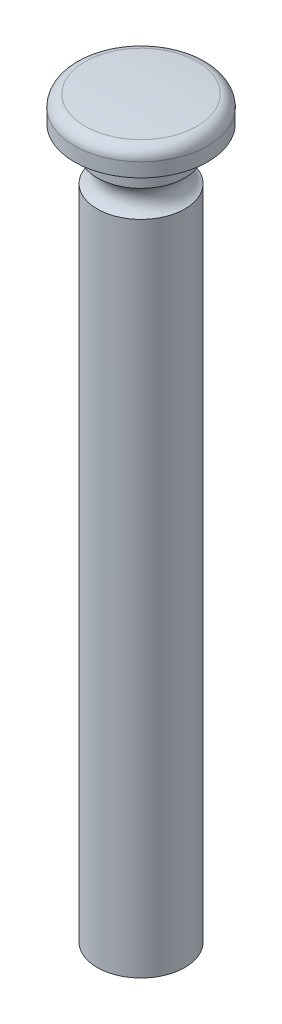
SolidWorks part; units mm, degrees
ref_plane "Front Plane" through (0, 0, 0) normal (0, 0, 1) x (1, 0, 0)
ref_plane "Top Plane" through (0, 0, 0) normal (0, 1, 0) x (1, 0, 0)
ref_plane "Right Plane" through (0, 0, 0) normal (1, 0, 0) x (0, 0, -1)
sketch "Sketch2" plane through (0, 0, 0) normal (0, 1, 0) x (1, 0, 0)
  circle A0 centre (0, 0) radius 9.525
extrude "Extrude1" add sketch "Sketch2" along normal blind 153.924
sketch "Sketch3" plane through (0, 153.924, 0) normal (0, 1, 0) x (-1, 0, 0)
  circle A0 centre (0, 0) radius 14.478
extrude "Extrude2" add sketch "Sketch3" along normal blind 5.334
dome "Dome1" faces to dome 1 distance 0.762 reverse direction no elliptical dome no face at (0, 159.258, 14.478) parameters "D1"=0.762
fillet "Fillet1" radius 2.54 1 edges at (0, 159.258, 14.478)
sketch "Sketch14" plane through (0, 0, 0) normal (0, 0, 1) x (1, 0, 0)
  line L0 (9.525, 153.924) -> (9.525, 145.542) construction
  line L1 (9.525, 0) -> (9.525, 153.924) construction
  line L2 (9.525, 145.542) -> (8.128, 145.542) construction
  line L3 (9.525, 145.542) -> (9.525, 142.621) construction
  line L4 (9.525, 148.463) -> (9.525, 142.621)
  line L5 (9.525, 145.542) -> (9.525, 148.463) construction
  line L6 (9.525, 145.542) -> (-9.525, 145.542) construction
  line L8 (0, 145.542) -> (0, 153.924) construction
  line L9 (-9.525, 153.924) -> (9.525, 153.924) construction
  line L10 (-9.525, 153.924) -> (-9.525, 0) construction
  arc A0 (9.525, 142.621) -> (9.525, 148.463) centre (10.7961, 145.542) cw
revolve "Cut-Revolve1" cut sketch "Sketch14" angle 360 about L8
